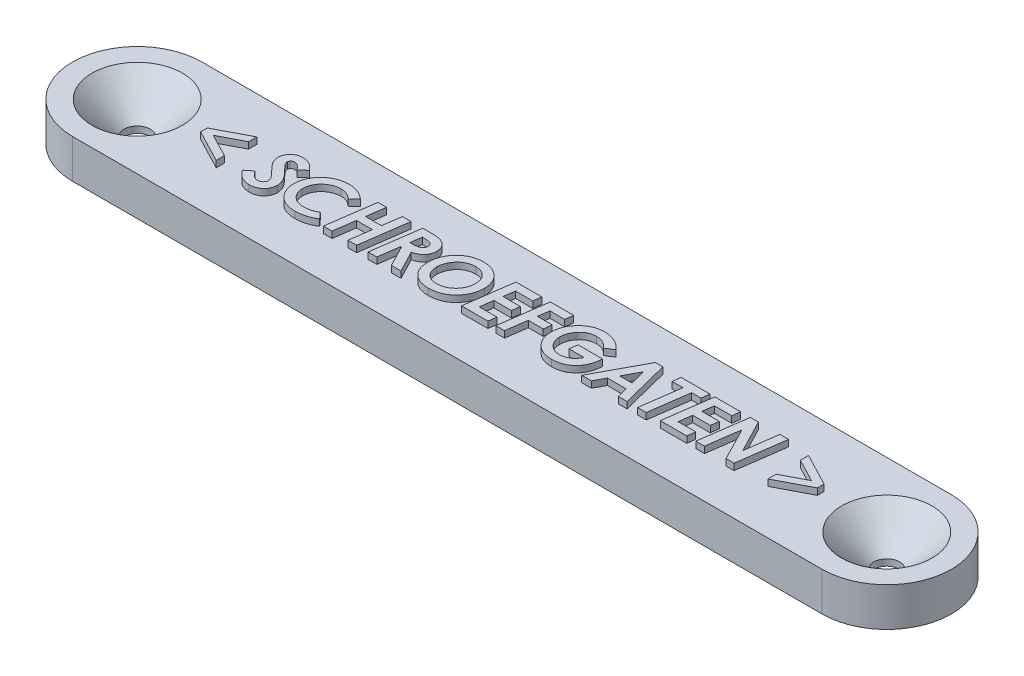
SolidWorks part; units mm, degrees
ref_plane "Front Plane" through (0, 0, 0) normal (0, 0, 1) x (1, 0, 0)
ref_plane "Top Plane" through (0, 0, 0) normal (0, 1, 0) x (1, 0, 0)
ref_plane "Right Plane" through (0, 0, 0) normal (1, 0, 0) x (0, 0, -1)
sketch "Sketch1" plane through (0, 0, 0) normal (0, 1, 0) x (1, 0, 0)
  line L0 (0, 0) -> (58, 0) construction
  line L1 (0, 0) -> (58, 0) construction
  line L2 (0, 5) -> (58, 5)
  line L3 (0, -5) -> (58, -5)
  circle A0 centre (0, 0) radius 1
  circle A1 centre (58, 0) radius 1
  arc A2 (0, 5) -> (0, -5) centre (0, 0) ccw
  arc A3 (58, -5) -> (58, 5) centre (58, 0) ccw
  point P5 (29, 0)
  dimension "D2" = 2
  dimension "D3" = 2
  dimension "D1" = 58
  dimension "D4" = 10
extrude "Boss-Extrude1" add sketch "Sketch1" along normal blind 3
chamfer "Chamfer1" distance 2.5 angle 45 2 edges at (58, 3, 1) (0, 3, 1)
sketch "Sketch2" plane through (0, 3, 0) normal (0, 1, 0) x (1, 0, 0)
  line L0 (-4.6648, -1.8) -> (62.6648, -1.8) construction
  line L1 (0, -5) -> (58, -5) construction
  line L2 (0, 0) -> (58, 0) construction
  arc A0 (0, 5) -> (0, -5) centre (0, 0) ccw construction
  arc A1 (58, -5) -> (58, 5) centre (58, 0) ccw construction
  text T0 "<b>< SCHROEFGATEN ></b>" font "Century Gothic" height in points 14
  dimension "D1" = 3.2
extrude "Boss-Extrude2" add sketch "Sketch2" along normal blind 0.5
